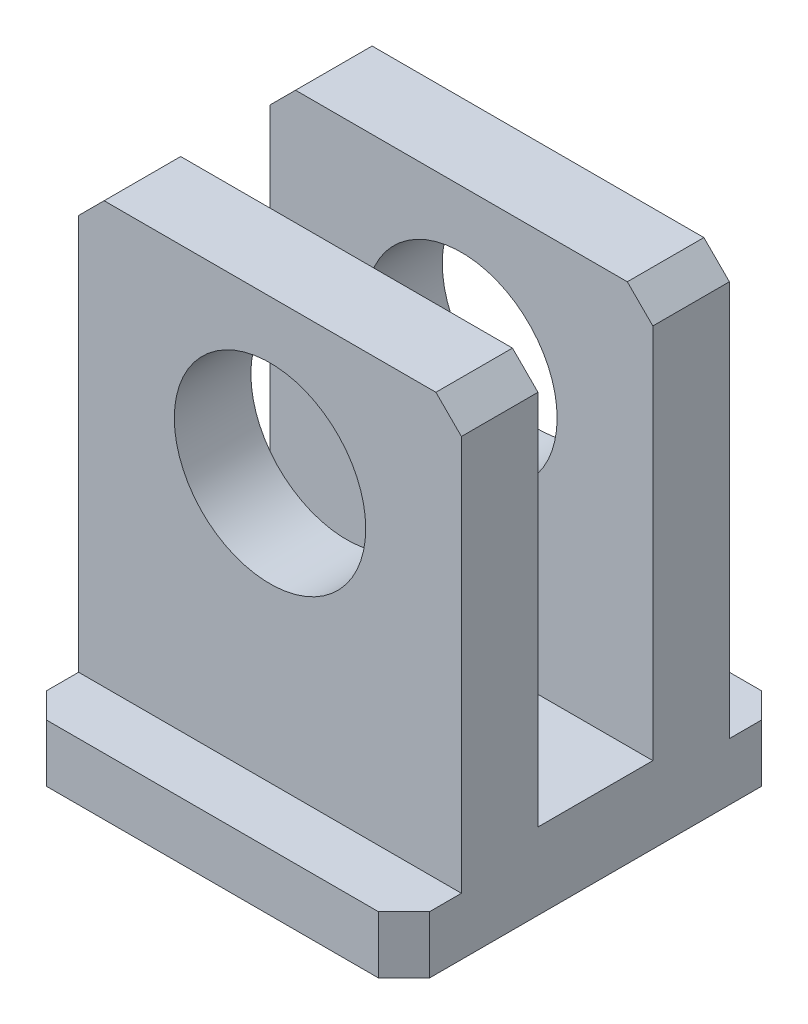
SolidWorks part; units mm, degrees
ref_plane "前视基准面" through (0, 0, 0) normal (0, 0, 1) x (1, 0, 0)
ref_plane "上视基准面" through (0, 0, 0) normal (0, 1, 0) x (1, 0, 0)
ref_plane "右视基准面" through (0, 0, 0) normal (1, 0, 0) x (0, 0, -1)
other "Configuration Table"
sketch "草图1" plane through (0, 0, 0) normal (0, 0, 1) x (1, 0, 0)
  line L0 (-13, 18.75) -> (-15, 16.75)
  line L1 (15, -18.75) -> (-15, -18.75)
  line L2 (15, -18.75) -> (15, 16.75)
  line L3 (13, 18.75) -> (-13, 18.75)
  line L4 (-15, -18.75) -> (-15, 16.75)
  line L5 (15, -18.75) -> (-15, 18.75) construction
  line L6 (15, 18.75) -> (-15, -18.75) construction
  line L7 (15, 16.75) -> (13, 18.75)
  point P0 (0, 0)
  point P6 (0, 0)
  dimension "D1" = 30
  dimension "D2" = 37.5
extrude "凸台-拉伸1" add sketch "草图1" along normal blind 6
sketch "草图8" plane through (0, 0, 6) normal (0, 0, 1) x (1, 0, 0)
  line L0 (-15, -14.25) -> (15, -14.25)
  line L1 (-15, 16.75) -> (-15, -18.75) construction
  line L2 (15, -18.75) -> (15, 16.75) construction
  line L3 (-15, -18.75) -> (15, -18.75) construction
  line L4 (15, 16.75) -> (13, 18.75) construction
  line L5 (15, -18.75) -> (15, 16.75) construction
  line L6 (-15, 16.75) -> (-15, -18.75) construction
  line L7 (-13, 18.75) -> (-15, 16.75) construction
  line L8 (13, 18.75) -> (-13, 18.75) construction
  line L9 (-15, -18.75) -> (15, -18.75)
  line L10 (15, 16.75) -> (13, 18.75)
  line L11 (15, -18.75) -> (15, 16.75)
  line L12 (-15, 16.75) -> (-15, -18.75)
  line L13 (-13, 18.75) -> (-15, 16.75)
  line L14 (13, 18.75) -> (-13, 18.75)
  circle A0 centre (0, 6.75) radius 7.5
  line M8 (15, -18.75) -> (15, 16.75)
  line M12 (-15, 16.75) -> (-15, -18.75)
  line M13 (-15, -18.75) -> (15, -18.75)
  dimension "D3" = 15
  dimension "D1" = 4.5
  dimension "D2" = 25.5
extrude "凸台-拉伸4" add sketch "草图8" along normal blind 4.5 contours L0 M12 M13 M8 region at (0, -16.5, 6)
chamfer "倒角1" distance 2 angle 45 1 edges at (-15, -16.5, 10.5)
chamfer "倒角2" distance 2 angle 45 1 edges at (15, -16.5, 10.5)
extrude "切除-拉伸2" cut sketch "草图8<5>" against normal up to next contours A0 region at (0, 6.75, 6)
sketch "草图8<5>" plane through (0, 0, 6) normal (0, 0, 1) x (1, 0, 0) same geometry as "草图8"
sketch "草图12" plane through (0, 0, 0) normal (1, 0, 0) x (0, 0, -1)
  line L0 (4.5, 11.2261) -> (4.5, -12.1899) construction
  line L1 (0, -18.75) -> (0, 16.75) construction
  line L2 (0, -0.75) -> (0, 14.25) construction
  dimension "D1" = 4.5
sketch "草图13" plane through (0, 0, 0) normal (0, 0, -1) x (-1, 0, 0)
  line L0 (15, 16.75) -> (15, -18.75) construction
  line L1 (-15, -18.75) -> (15, -18.75)
  line L2 (-15, -18.75) -> (-15, -12.75)
  line L3 (-15, -12.75) -> (15, -12.75)
  line L4 (15, -18.75) -> (15, -12.75)
  dimension "D1" = 6
extrude "凸台-拉伸5" add sketch "草图13" along normal blind 4.5
ref_plane "基准面1" through (0, 0, -4.5) normal (0, 0, -1) x (-1, 0, 0)
mirror "镜向4" about plane through (0, 0, -4.5) normal (0, 0, -1) of "凸台-拉伸5", "凸台-拉伸1", "倒角2", "切除-拉伸2", "凸台-拉伸4", "倒角1"
sketch "草图7" plane through (0, 0, 0) normal (1, 0, 0) x (0, 0, -1)
  line L0 (4.5, 18.3522) -> (4.5, -8.5849) construction
  dimension "D1" = 4.5
